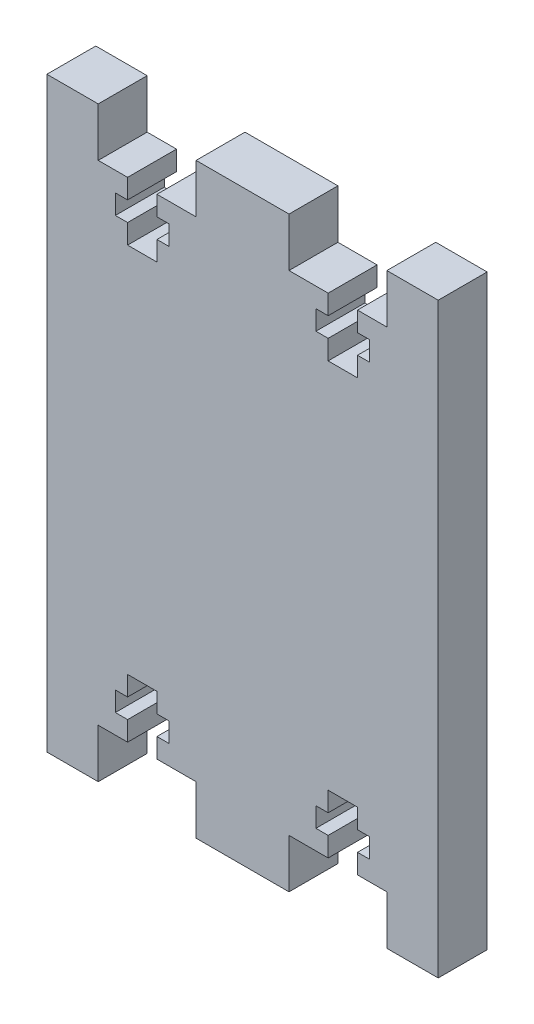
SolidWorks part; units mm, degrees
ref_plane "Front Plane" through (0, 0, 0) normal (0, 0, 1) x (1, 0, 0)
ref_plane "Top Plane" through (0, 0, 0) normal (0, 1, 0) x (1, 0, 0)
ref_plane "Right Plane" through (0, 0, 0) normal (1, 0, 0) x (0, 0, -1)
sketch "Sketch1" plane through (0, 0, 0) normal (0, 0, 1) x (1, 0, 0)
  line L1 (-87.1368, 14.9253) -> (-47.1368, 14.9253)
  line L2 (-87.1368, 14.9253) -> (-87.1368, 69.9253)
  line L3 (-87.1368, 69.9253) -> (-47.1368, 69.9253)
  line L4 (-47.1368, 14.9253) -> (-47.1368, 69.9253)
  dimension "D1" = 40
  dimension "D2" = 55
extrude "Boss-Extrude1" add sketch "Sketch1" along normal blind 5
sketch "Sketch2" plane through (0, 0, 5) normal (0, 0, 1) x (1, 0, 0)
  line L1 (-78.8868, 63.9253) -> (-75.8868, 63.9253)
  line L2 (-78.8868, 63.9253) -> (-78.8868, 69.9253)
  line L3 (-78.8868, 69.9253) -> (-75.8868, 69.9253)
  line L4 (-75.8868, 63.9253) -> (-75.8868, 69.9253)
  line L5 (-78.8868, 63.9253) -> (-75.8868, 69.9253) construction
  line L6 (-78.8868, 69.9253) -> (-75.8868, 63.9253) construction
  line L7 (-74.6368, 66.9253) -> (-59.6368, 66.9253) construction
  line L8 (-80.1368, 67.9253) -> (-74.6368, 67.9253)
  line L9 (-80.1368, 67.9253) -> (-80.1368, 65.9253)
  line L10 (-80.1368, 65.9253) -> (-74.6368, 65.9253)
  line L11 (-74.6368, 67.9253) -> (-74.6368, 65.9253)
  line L12 (-80.1368, 67.9253) -> (-74.6368, 65.9253) construction
  line L13 (-80.1368, 65.9253) -> (-74.6368, 67.9253) construction
  line L14 (-67.1368, 66.9253) -> (-67.1368, 69.9253) construction
  line L15 (-47.1368, 69.9253) -> (-87.1368, 69.9253) construction
  line L17 (-47.1368, 14.9253) -> (-47.1368, 69.9253) construction
  line L18 (-87.1368, 69.9253) -> (-81.8868, 69.9253)
  line L19 (-87.1368, 69.9253) -> (-87.1368, 74.9253)
  line L20 (-87.1368, 74.9253) -> (-81.8868, 74.9253)
  line L21 (-81.8868, 69.9253) -> (-81.8868, 74.9253)
  line L22 (-71.8868, 69.9253) -> (-62.3868, 69.9253)
  line L23 (-71.8868, 69.9253) -> (-71.8868, 74.9253)
  line L24 (-71.8868, 74.9253) -> (-62.3868, 74.9253)
  line L25 (-58.3868, 63.9253) -> (-55.3868, 63.9253)
  line L26 (-58.3868, 63.9253) -> (-58.3868, 69.9253)
  line L27 (-58.3868, 69.9253) -> (-55.3868, 69.9253)
  line L28 (-55.3868, 63.9253) -> (-55.3868, 69.9253)
  line L29 (-59.6368, 67.9253) -> (-54.1368, 67.9253)
  line L30 (-59.6368, 67.9253) -> (-59.6368, 65.9253)
  line L31 (-59.6368, 65.9253) -> (-54.1368, 65.9253)
  line L32 (-54.1368, 67.9253) -> (-54.1368, 65.9253)
  line L33 (-58.3868, 63.9253) -> (-55.3868, 69.9253) construction
  line L34 (-58.3868, 69.9253) -> (-55.3868, 63.9253) construction
  line L35 (-59.6368, 67.9253) -> (-54.1368, 65.9253) construction
  line L36 (-59.6368, 65.9253) -> (-54.1368, 67.9253) construction
  line L37 (-62.3868, 69.9253) -> (-62.3868, 74.9253)
  line L38 (-47.1368, 69.9253) -> (-52.3868, 69.9253)
  line L39 (-47.1368, 69.9253) -> (-47.1368, 74.9253)
  line L40 (-47.1368, 74.9253) -> (-52.3868, 74.9253)
  line L41 (-52.3868, 69.9253) -> (-52.3868, 74.9253)
  point P0 (-77.3868, 66.9253)
  point P7 (-77.3868, 66.9253)
  point P23 (-56.8868, 66.9253)
  point P28 (-56.8868, 66.9253)
  line M29 (-87.1368, 69.9253) -> (-87.1368, 14.9253)
  line M30 (-87.1368, 14.9253) -> (-47.1368, 14.9253)
  line M31 (-47.1368, 14.9253) -> (-47.1368, 69.9253)
  line M32 (-47.1368, 69.9253) -> (-87.1368, 69.9253)
  dimension "D1" = 2
  dimension "D2" = 5.5
  dimension "D3" = 3
  dimension "D4" = 6
  dimension "D6" = 5
  dimension "D7" = 3
  dimension "D8" = 4
  dimension "D9" = 4
  dimension "D10" = 3
  dimension "D11" = 15
  dimension "D5" = 2
extrude "Cut-Extrude1" cut sketch "Sketch2" against normal blind 10 flip side to cut contours L29 L32 L31 L28 L25 L26 L30 L4 L8 L11 L10 L1 L2 L9 M32 M29 M30 M31 region at (-67.1368, 41.9021, 5)
extrude "Boss-Extrude2" add sketch "Sketch2<3>" against normal blind 5 contours L21 L20 L19 M32 | L37 L24 L23 M32 | L41 L39 L40 M32 region at (-84.5118, 72.4253, 5) region at (-49.7618, 72.4253, 5) region at (-67.1368, 72.4253, 5)
sketch "Sketch2<3>" plane through (0, 0, 5) normal (0, 0, 1) x (1, 0, 0) same geometry as "Sketch2"
ref_plane "Plane1" through (0, 44.9253, 0) normal (0, 1, 0) x (-1, 0, 0)
mirror "Mirror1" about plane through (0, 44.9253, 0) normal (0, 1, 0) of "Cut-Extrude1", "Boss-Extrude2"
